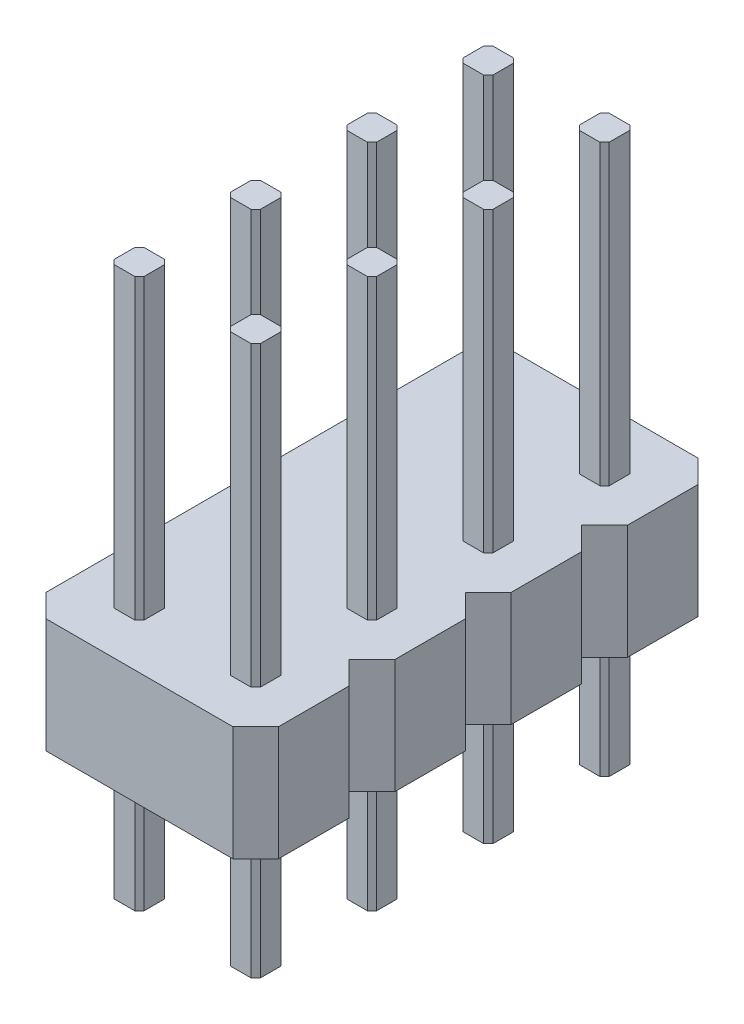
SolidWorks part; units mm, degrees
ref_plane "前视基准面" through (0, 0, 0) normal (0, 0, 1) x (1, 0, 0)
ref_plane "上视基准面" through (0, 0, 0) normal (0, 1, 0) x (1, 0, 0)
ref_plane "右视基准面" through (0, 0, 0) normal (1, 0, 0) x (0, 0, -1)
sketch "草图1" plane through (0, 0, 0) normal (0, 1, 0) x (1, 0, 0)
  line L0 (-0.225, -0.325) -> (-0.325, -0.225)
  line L1 (0.225, -0.325) -> (-0.225, -0.325)
  line L2 (0.325, -0.225) -> (0.325, 0.225)
  line L3 (0.225, 0.325) -> (-0.225, 0.325)
  line L4 (-0.325, -0.225) -> (-0.325, 0.225)
  line L5 (0.325, -0.325) -> (-0.325, 0.325) construction
  line L6 (0.325, 0.325) -> (-0.325, -0.325) construction
  line L7 (0.325, -0.225) -> (0.225, -0.325)
  line L8 (0.325, 0.225) -> (0.225, 0.325)
  line L9 (-0.225, 0.325) -> (-0.325, 0.225)
  point P0 (0, 0)
  dimension "D1" = 0.65
extrude "凸台-拉伸1" add sketch "草图1" along normal blind 12
pattern_linear "阵列(线性)1" count 2 spacing 2.54 along (1, 0, 0) of bodies 106
ref_plane "基准面1" through (0, 3, 0) normal (0, -1, 0) x (-1, 0, 0)
sketch "草图2" plane through (0, 3, 0) normal (0, -1, 0) x (-1, 0, 0)
  line L0 (0.325, 0) -> (-2.865, 0) construction
  line L1 (0.325, 0.225) -> (0.325, -0.225) construction
  line L2 (-2.865, -0.225) -> (-2.865, 0.225) construction
  line L3 (-3.31, 1.27) -> (-3.81, 0.77)
  line L4 (0.77, -1.27) -> (-3.31, -1.27)
  line L5 (1.27, -0.77) -> (1.27, 0.77)
  line L6 (0.77, 1.27) -> (-3.31, 1.27)
  line L7 (-3.81, -0.77) -> (-3.81, 0.77)
  line L8 (1.27, -1.27) -> (-3.81, 1.27) construction
  line L9 (1.27, 1.27) -> (-3.81, -1.27) construction
  line L10 (-3.31, -1.27) -> (-3.81, -0.77)
  line L11 (1.27, -0.77) -> (0.77, -1.27)
  line L12 (1.27, 0.77) -> (0.77, 1.27)
  point P6 (-1.27, 0)
  dimension "D1" = 5.08
  dimension "D2" = 2.54
extrude "凸台-拉伸2" add sketch "草图2" against normal blind 2.5
pattern_linear "阵列(线性)2" count 4 spacing 2.54 along (0, 0, -1) of bodies 108
combine bodies "组合1" operation type add bodies to combine 108 109 110 111
